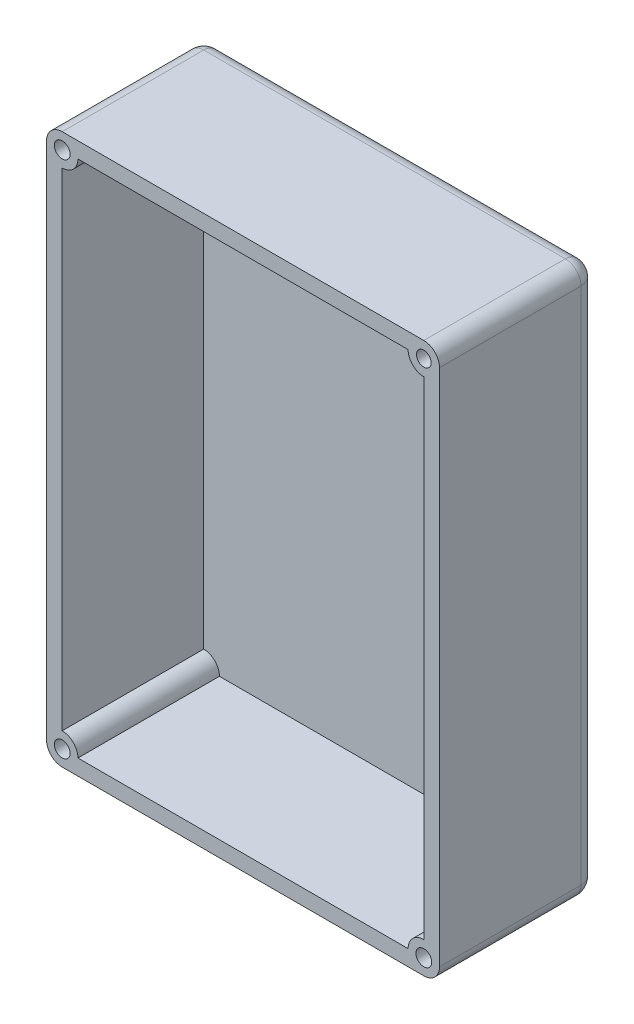
SolidWorks part; units mm, degrees
ref_plane "Front Plane" through (0, 0, 0) normal (0, 0, 1) x (1, 0, 0)
ref_plane "Top Plane" through (0, 0, 0) normal (0, 1, 0) x (1, 0, 0)
ref_plane "Right Plane" through (0, 0, 0) normal (1, 0, 0) x (0, 0, -1)
sketch "Sketch1" plane through (0, 0, 0) normal (0, 0, 1) x (1, 0, 0)
  line L1 (0, 0) -> (250, 0)
  line L2 (0, 0) -> (0, -350)
  line L3 (0, -350) -> (250, -350)
  line L4 (250, 0) -> (250, -350)
  dimension "D1" = 350
  dimension "D2" = 250
extrude "Boss-Extrude1" add sketch "Sketch1" against normal blind 100
sketch "Sketch2" plane through (0, 0, 0) normal (0, 0, 1) x (1, 0, 0)
  line L0 (250, -350) -> (250, 0) construction
  line L1 (10, -10) -> (240, -10)
  line L2 (10, -10) -> (10, -340)
  line L3 (10, -340) -> (240, -340)
  line L4 (240, -10) -> (240, -340)
  line L5 (250, 0) -> (0, 0) construction
  line L6 (0, -350) -> (250, -350) construction
  line L8 (0, 0) -> (0, -350) construction
  dimension "D1" = 10
  dimension "D2" = 10
  dimension "D3" = 10
  dimension "D4" = 10
extrude "Cut-Extrude1" cut sketch "Sketch2" against normal blind 90
fillet "Fillet1" radius 10 8 edges at (0, -350, -50) (250, -350, -50) (125, -350, -100) (0, -175, -100) (250, -175, -100) (125, 0, -100) (250, 0, -50) (0, 0, -50)
sketch "Sketch3" plane through (0, 0, -90) normal (0, 0, 1) x (1, 0, 0)
  line L1 (10, -340) -> (20, -340)
  line L2 (10, -340) -> (10, -330)
  line L3 (10, -330) -> (20, -330)
  line L4 (20, -340) -> (20, -330)
  dimension "D1" = 10
  dimension "D2" = 10
extrude "Boss-Extrude2" add sketch "Sketch3" along normal blind 90
sketch "Sketch4" plane through (0, 0, -90) normal (0, 0, 1) x (1, 0, 0)
  line L1 (240, -340) -> (230, -340)
  line L2 (240, -340) -> (240, -330.0046)
  line L3 (240, -330.0046) -> (230, -330.0046)
  line L4 (230, -340) -> (230, -330.0046)
  dimension "D1" = 10
extrude "Boss-Extrude3" add sketch "Sketch4" along normal blind 90
sketch "Sketch5" plane through (0, 0, -90) normal (0, 0, 1) x (1, 0, 0)
  line L1 (240, -10) -> (230, -10)
  line L2 (240, -10) -> (240, -20)
  line L3 (240, -20) -> (230, -20)
  line L4 (230, -10) -> (230, -20)
  line L11 (10, -10) -> (20, -10)
  line L12 (10, -10) -> (10, -20)
  line L13 (10, -20) -> (20, -20)
  line L14 (20, -10) -> (20, -20)
  dimension "D1" = 10
  dimension "D2" = 10
  dimension "D3" = 10
  dimension "D4" = 10
extrude "Boss-Extrude4" add sketch "Sketch5" along normal blind 90
fillet "Fillet2" radius 10 1 edges at (230, -20, -45)
fillet "Fillet3" radius 10 3 edges at (230, -330.0046, -45) (20, -330, -45) (20, -20, -45)
sketch "Sketch6" plane through (0, 0, 0) normal (0, 0, 1) x (1, 0, 0)
  line L0 (240, -330.0046) -> (240, -20) construction
  line L3 (230, -10) -> (20, -10) construction
  circle A0 centre (240, -10) radius 4.668
  point P4 (0, 0)
  point P5 (0, 0)
  point P6 (0, 0)
  point P7 (0, 0)
  point P8 (253.5156, -11.3367)
  point P13 (242.6266, -9.5548)
  dimension "D1" = 0
  dimension "D2" = 0
extrude "Cut-Extrude2" cut sketch "Sketch6" against normal blind 10
sketch "Sketch7" plane through (0, 0, 0) normal (0, 0, 1) x (1, 0, 0)
  circle A0 centre (10, -10) radius 5
extrude "Cut-Extrude3" cut sketch "Sketch7" against normal blind 10
sketch "Sketch8" plane through (0, 0, 0) normal (0, 0, 1) x (1, 0, 0)
  circle A0 centre (240, -340.0046) radius 5
extrude "Cut-Extrude4" cut sketch "Sketch8" against normal blind 10 contours A0
sketch "Sketch9" plane through (0, 0, 0) normal (0, 0, 1) x (1, 0, 0)
  circle A0 centre (10, -340) radius 5
extrude "Cut-Extrude5" cut sketch "Sketch9" against normal blind 10
